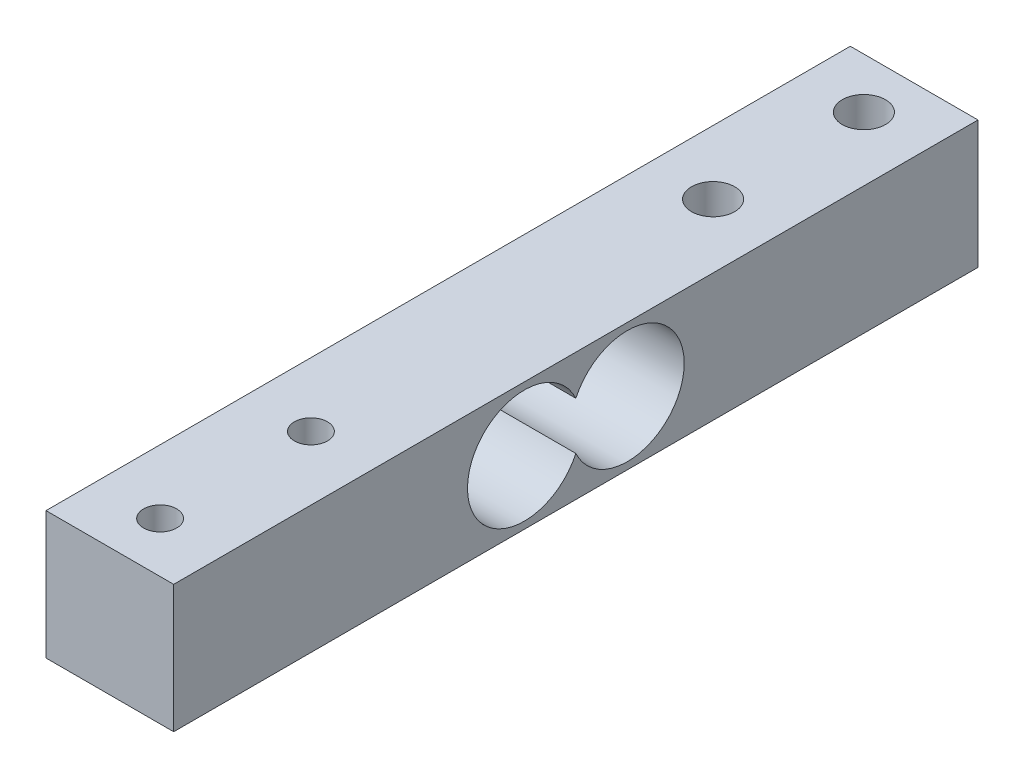
SolidWorks part; units mm, degrees
ref_plane "Front Plane" through (0, 0, 0) normal (0, 0, 1) x (1, 0, 0)
ref_plane "Top Plane" through (0, 0, 0) normal (0, 1, 0) x (1, 0, 0)
ref_plane "Right Plane" through (0, 0, 0) normal (1, 0, 0) x (0, 0, -1)
sketch "Sketch1" plane through (0, 0, 0) normal (0, 0, 1) x (1, 0, 0)
  line L1 (-6.35, -6.35) -> (6.35, -6.35)
  line L2 (-6.35, -6.35) -> (-6.35, 6.35)
  line L3 (-6.35, 6.35) -> (6.35, 6.35)
  line L4 (6.35, -6.35) -> (6.35, 6.35)
  point P8 (0, -6.35)
  point P9 (-6.35, 0)
  dimension "D1" = 12.7
  dimension "D2" = 12.7
extrude "Boss-Extrude1" add sketch "Sketch1" along normal mid plane 80
sketch "Sketch2" plane through (6.35, 0, 0) normal (1, 0, 0) x (0, 0, -1)
  line L0 (-40, -6.35) -> (-40, 6.35) construction
  line L1 (-5.1266, 0) -> (5.1266, 0) construction
  line L2 (-40, -6.35) -> (40, -6.35) construction
  arc A0 (0, 2.375) -> (0, -2.375) centre (-5.1266, 0) ccw
  arc A1 (0, -2.375) -> (0, 2.375) centre (5.1266, 0) ccw
  point P7 (-40, 0)
  point P9 (0, -6.35)
  point P10 (0, 0)
  dimension "D1" = 11.3
  dimension "D2" = 4.75
extrude "Cut-Extrude1" cut sketch "Sketch2" against normal through all
sketch "Sketch3" plane through (0, 6.35, 0) normal (0, 1, 0) x (1, 0, 0)
  line L0 (-6.35, 40) -> (6.35, 40) construction
  circle A0 centre (0, 35) radius 2.15
  circle A1 centre (0, 20) radius 2.15
  dimension "D3" = 4.3
  dimension "D2" = 5
  dimension "D1" = 15
extrude "Cut-Extrude2" cut sketch "Sketch3" against normal through all
sketch "Sketch4" plane through (0, 6.35, 0) normal (0, 1, 0) x (1, 0, 0)
  line L0 (6.35, -40) -> (-6.35, -40) construction
  circle A0 centre (0, -35) radius 1.65
  circle A1 centre (0, -20) radius 1.65
  point P8 (0, -40)
  dimension "D3" = 3.3
  dimension "D1" = 5
  dimension "D2" = 15
extrude "Cut-Extrude3" cut sketch "Sketch4" against normal through all
sketch "Sketch8" plane through (0, -6.35, 0) normal (0, -1, 0) x (1, 0, 0)
  line L0 (-6.35, -15) -> (6.35, -15)
  line L1 (-6.35, 40) -> (-6.35, -40) construction
  line L2 (6.35, 40) -> (6.35, -40) construction
  line L4 (-6.35, 15) -> (6.35, 15)
  line L5 (-6.35, 40) -> (6.35, 40) construction
  line L6 (-6.35, -40) -> (6.35, -40) construction
  dimension "D1" = 25
  dimension "D2" = 25
split line "Split Line4"
sketch "Sketch9" plane through (0, 0, 0) normal (0, 1, 0) x (1, 0, 0)
  line L0 (-6.35, -27.5) -> (6.35, -27.5) construction
  line L1 (-6.35, -40) -> (-6.35, 40) construction
  line L2 (6.35, -40) -> (6.35, 40) construction
  line L3 (6.35, -40) -> (-6.35, -40) construction
  dimension "D1" = 12.5
ref_axis "Axis1" through (-6.35, 0, 27.5) along (1, 0, 0)
ref_axis "Axis2" through (0, 0, -4) along (0, 0, 1)
